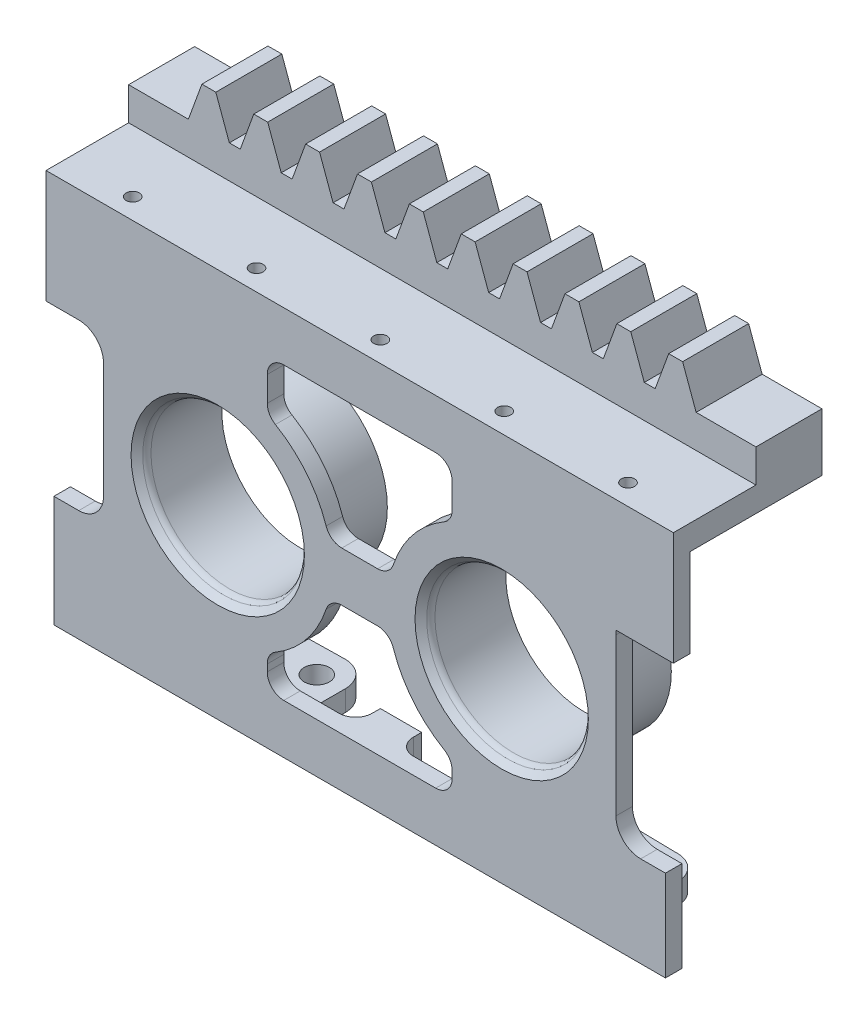
SolidWorks part; units mm, degrees
material "6061 合金"
ref_plane "Front" through (0, 0, 0) normal (0, 0, 1) x (1, 0, 0)
ref_plane "Top" through (0, 0, 0) normal (0, 1, 0) x (1, 0, 0)
ref_plane "Right" through (0, 0, 0) normal (1, 0, 0) x (0, 0, -1)
sketch "Sketch1" plane through (0, 0, 0) normal (0, 0, 1) x (1, 0, 0)
  line L1 (0, 0) -> (213.6283, 0)
  line L2 (0, 0) -> (0, -8)
  line L3 (0, -8) -> (213.6283, -8)
  line L4 (213.6283, 0) -> (213.6283, -8)
  dimension "D1" = 8
  dimension "L" = 213.6283
extrude "Extrude1" add sketch "Sketch1" along normal blind 8
sketch "Sketch2" plane through (0, 0, 8) normal (0, 0, 1) x (1, 0, 0)
  line L0 (0, 0) -> (1.6379, 4.5)
  line L1 (1.6379, 4.5) -> (3.3236, 4.5)
  line L2 (3.3236, 4.5) -> (4.9614, 0)
  line L3 (213.6283, 0) -> (0, 0) construction
  line L4 (0, 0) -> (4.9614, 0)
  line L5 (0.9099, 2.5) -> (4.0515, 2.5) construction
  dimension "alpha2" = 70
  dimension "alpha" = 110
  dimension "ha" = 2
  dimension "hf" = 2.5
  dimension "S" = 3.1416
extrude "Extrude2" add sketch "Sketch2" against normal up to surface (8 mm away) up to face at (106.8142, -4, 0)
pattern_linear "LPattern1" count 34 spacing 6.2832 along (1, 0, 0) of "Extrude2"
sketch "草图1" plane through (0, 0, 8) normal (0, 0, 1) x (1, 0, 0)
  line L1 (213.6283, -8) -> (74.0765, -8)
  line L2 (213.6283, -8) -> (213.6283, 20)
  line L3 (213.6283, 20) -> (74.0765, 20)
  line L4 (74.0765, -8) -> (74.0765, 20)
  dimension "D1" = 28
extrude "切除-拉伸1" cut sketch "草图1" against normal blind 10
sketch "草图2" plane through (0, 0, 0) normal (0, 1, 0) x (1, 0, 0)
  line L1 (0, 0) -> (4.9614, 0)
  line L2 (0, 0) -> (0, -8)
  line L3 (0, -8) -> (4.9614, -8)
  line L4 (4.9614, 0) -> (4.9614, -8)
  line L5 (69.115, 0) -> (74.0765, 0)
  line L6 (69.115, 0) -> (69.115, -8)
  line L7 (69.115, -8) -> (74.0765, -8)
  line L8 (74.0765, 0) -> (74.0765, -8)
extrude "切除-拉伸2" cut sketch "草图2" along normal blind 10
sketch "草图3" plane through (0, 0, 8) normal (0, 0, 1) x (1, 0, 0)
  line L0 (0, 0) -> (0, -8) construction
  line L1 (0, -7) -> (74.0765, -7)
  line L2 (0, -7) -> (0, -8)
  line L3 (0, -8) -> (74.0765, -8)
  line L4 (74.0765, -7) -> (74.0765, -8)
  line L5 (74.0765, 0) -> (67.7933, 0) construction
  dimension "D1" = 7
extrude "切除-拉伸3" cut sketch "草图3" against normal blind 10
sketch "草图4" plane through (0, 0, 8) normal (0, 0, 1) x (1, 0, 0)
  line L0 (74.0765, 0) -> (74.0765, -7) construction
  line L1 (0, -7) -> (74.0765, -7)
  line L2 (0, -7) -> (0, -5)
  line L3 (0, -5) -> (74.0765, -5)
  line L4 (74.0765, -7) -> (74.0765, -5)
  dimension "D1" = 2
extrude "凸台-拉伸1" add sketch "草图4" along normal blind 8
sketch "草图5" plane through (0, 0, 16) normal (0, 0, 1) x (1, 0, 0)
  line L0 (74.0765, -7) -> (74.0765, -5) construction
  line L1 (0, -5) -> (74.0765, -5)
  line L2 (0, -5) -> (0, -50.4)
  line L3 (0, -50.4) -> (74.0765, -50.4)
  line L4 (74.0765, -5) -> (74.0765, -50.4)
  dimension "D1" = 45.4
extrude "凸台-拉伸2" add sketch "草图5" along normal blind 2
sketch "草图6" plane through (0, -50.4, 0) normal (0, -1, 0) x (1, 0, 0)
  line L0 (26.8382, 9.55) -> (26.8382, 11.9) construction
  line L1 (26.8382, 9.55) -> (26.8382, 18)
  line L2 (6.8382, 14.8) -> (6.8382, 9.6986) construction
  line L3 (6.8382, 18) -> (6.8382, 9.6986)
  line L4 (9.7846, 6.6991) -> (23.6828, 6.4505)
  line L5 (0, 18) -> (74.0765, 18) construction
  line L6 (6.8382, 18) -> (26.8382, 18)
  arc A0 (22.714, 10.1818) -> (24.5625, 9.4182) centre (23.6382, 9.8) ccw construction
  arc A1 (10.0382, 8.8) -> (10.0382, 10.8) centre (10.0382, 9.8) ccw construction
  arc A2 (22.714, 10.1818) -> (24.5625, 9.4182) centre (23.6382, 9.8) ccw construction
  arc A3 (10.0382, 8.8) -> (10.0382, 10.8) centre (10.0382, 9.8) ccw construction
  arc A4 (25.5982, 7.07) -> (26.8382, 9.55) centre (23.7382, 9.55) ccw construction
  arc A5 (23.6828, 6.4505) -> (26.8382, 9.55) centre (23.7382, 9.55) ccw
  arc A6 (6.8382, 9.6986) -> (8.2948, 7.1261) centre (9.8382, 9.6986) ccw construction
  arc A7 (6.8382, 9.6986) -> (9.7846, 6.6991) centre (9.8382, 9.6986) ccw
  circle A8 centre (10.0382, 9.8) radius 1.525
  circle A9 centre (23.6382, 9.8) radius 1.525
  dimension "D1" = 3.05
extrude "凸台-拉伸3" add sketch "草图6" against normal blind 1.7
ref_plane "基准面1" through (37.0382, 0, 0) normal (-1, 0, 0) x (0, 0, 1)
mirror "镜向1" about plane through (37.0382, 0, 0) normal (-1, 0, 0) of "凸台-拉伸3"
sketch "草图7" plane through (0, 0, 18) normal (0, 0, 1) x (1, 0, 0)
  arc A0 (54.2382, -18.15) -> (43.7357, -27.7) centre (54.2382, -28.7) ccw construction
  arc A1 (30.3407, -27.7) -> (19.8382, -18.15) centre (19.8382, -28.7) ccw construction
  arc A2 (54.2382, -18.15) -> (43.7357, -27.7) centre (54.2382, -28.7) ccw construction
  arc A3 (30.3407, -27.7) -> (19.8382, -18.15) centre (19.8382, -28.7) ccw construction
  circle A4 centre (54.2382, -28.7) radius 10.55
  circle A5 centre (19.8382, -28.7) radius 10.55
  circle A6 centre (54.2382, -28.7) radius 9.5
  circle A7 centre (19.8382, -28.7) radius 9.5
  dimension "D1" = 21.1
  dimension "D2" = 19
extrude "凸台-拉伸4" add sketch "草图7" against normal blind 10
sketch "草图8" plane through (0, 0, 16) normal (0, 0, -1) x (-1, 0, 0)
  circle A1 centre (-19.8382, -28.7) radius 9.5
  circle A2 centre (-19.8382, -28.7) radius 9.5
  circle A3 centre (-54.2382, -28.7) radius 9.5
  circle A4 centre (-54.2382, -28.7) radius 9.5
  dimension "D1" = 0
  dimension "D2" = 0
extrude "切除-拉伸4" cut sketch "草图8" against normal blind 7
sketch "草图9" plane through (0, 0, 18) normal (0, 0, 1) x (1, 0, 0)
  line L0 (0, -5) -> (0, -50.4) construction
  line L1 (-6, -37.7) -> (6, -37.7)
  line L2 (-6, -37.7) -> (-6, -17.7)
  line L3 (-6, -17.7) -> (6, -17.7)
  line L4 (6, -37.7) -> (6, -17.7)
  line L5 (-6, -37.7) -> (6, -17.7) construction
  line L6 (-6, -17.7) -> (6, -37.7) construction
  line L7 (74.0765, -50.4) -> (74.0765, -5) construction
  line L8 (68.0765, -40.2) -> (80.0765, -40.2)
  line L9 (68.0765, -40.2) -> (68.0765, -15.2)
  line L10 (68.0765, -15.2) -> (80.0765, -15.2)
  line L11 (80.0765, -40.2) -> (80.0765, -15.2)
  line L12 (68.0765, -40.2) -> (80.0765, -15.2) construction
  line L13 (68.0765, -15.2) -> (80.0765, -40.2) construction
  point P0 (0, -27.7)
  point P7 (74.0765, -27.7)
  dimension "D1" = 25
  dimension "D2" = 20
  dimension "D3" = 12
extrude "切除-拉伸5" cut sketch "草图9" against normal blind 7
fillet "圆角1" radius 3 4 edges at (68.0765, -15.2, 17) (68.0765, -40.2, 17) (6, -17.7, 17) (6, -37.7, 17)
sketch "草图10" plane through (0, -50.4, 0) normal (0, -1, 0) x (1, 0, 0)
  line L0 (37.0382, 16) -> (37.0382, 6) construction
  line L1 (26.8382, 16) -> (47.2382, 16) construction
  line L2 (37.0382, 9.185) -> (37.0382, -9.185) construction
  line L4 (34.0382, 6) -> (40.0382, 6)
  line L5 (34.0382, 6) -> (34.0382, 16)
  line L6 (34.0382, 16) -> (40.0382, 16)
  line L7 (40.0382, 6) -> (40.0382, 16)
  line L8 (34.0382, 6) -> (40.0382, 16) construction
  line L9 (34.0382, 16) -> (40.0382, 6) construction
  point P6 (37.0382, 11)
  dimension "D1" = 6
  dimension "D2" = 10
extrude "凸台-拉伸5" [suppressed] add sketch "草图10" against normal blind 2 and the other way blind 0.8
sketch "草图12" [suppressed] plane through (0, -49.4, 0) normal (0, -1, 0) x (1, 0, 0)
  line L0 (0, 18) -> (74.0765, 18) construction
  line L1 (34.0382, 16) -> (40.0382, 16)
  line L2 (34.0382, 16) -> (34.0382, 18)
  line L3 (34.0382, 18) -> (40.0382, 18)
  line L4 (40.0382, 16) -> (40.0382, 18)
  line L5 (40.0382, 6) -> (40.0382, 16) construction
extrude "凸台-拉伸6" [suppressed] add sketch "草图12" along normal up to surface (0.8 mm away) up to face at (72.5057, 0, 4)
fillet "圆角2" [suppressed] radius 3
sketch "草图13" plane through (0, -50.4, 0) normal (0, -1, 0) x (1, 0, 0)
  line L12 (74.0765, 16) -> (74.0765, 18)
  line L13 (74.0765, 18) -> (0, 18)
  line L14 (0, 18) -> (0, 16)
  line L15 (0, 16) -> (6.8382, 16)
  line L16 (6.8382, 16) -> (6.8382, 9.6986)
  line L17 (9.7846, 6.6991) -> (23.6828, 6.4505)
  line L18 (26.8382, 9.55) -> (26.8382, 16)
  line L19 (26.8382, 16) -> (47.2382, 16)
  line L20 (47.2382, 16) -> (47.2382, 9.55)
  line L21 (50.3937, 6.4505) -> (64.2919, 6.6991)
  line L22 (67.2382, 9.6986) -> (67.2382, 16)
  line L23 (67.2382, 16) -> (74.0765, 16)
  line L24 (74.0765, 16) -> (74.0765, 18)
  line L25 (74.0765, 18) -> (0, 18)
  line L26 (0, 18) -> (0, 16)
  line L27 (0, 16) -> (6.8382, 16)
  line L28 (6.8382, 16) -> (6.8382, 9.6986)
  line L29 (9.7846, 6.6991) -> (23.6828, 6.4505)
  line L30 (26.8382, 9.55) -> (26.8382, 16)
  line L31 (26.8382, 16) -> (47.2382, 16)
  line L32 (47.2382, 16) -> (47.2382, 9.55)
  line L33 (50.3937, 6.4505) -> (64.2919, 6.6991)
  line L34 (67.2382, 9.6986) -> (67.2382, 16)
  line L35 (67.2382, 16) -> (74.0765, 16)
  circle A0 centre (64.0382, 9.8) radius 1.525 construction
  circle A1 centre (50.4382, 9.8) radius 1.525 construction
  circle A2 centre (23.6382, 9.8) radius 1.525 construction
  circle A3 centre (10.0382, 9.8) radius 1.525 construction
  arc A4 (6.8382, 9.6986) -> (9.7846, 6.6991) centre (9.8382, 9.6986) ccw
  arc A5 (23.6828, 6.4505) -> (26.8382, 9.55) centre (23.7382, 9.55) ccw
  arc A6 (47.2382, 9.55) -> (50.3937, 6.4505) centre (50.3382, 9.55) ccw
  arc A7 (64.2919, 6.6991) -> (67.2382, 9.6986) centre (64.2382, 9.6986) ccw
  arc A8 (6.8382, 9.6986) -> (9.7846, 6.6991) centre (9.8382, 9.6986) ccw
  arc A9 (23.6828, 6.4505) -> (26.8382, 9.55) centre (23.7382, 9.55) ccw
  arc A10 (47.2382, 9.55) -> (50.3937, 6.4505) centre (50.3382, 9.55) ccw
  arc A11 (64.2919, 6.6991) -> (67.2382, 9.6986) centre (64.2382, 9.6986) ccw
  circle A12 centre (64.0382, 9.8) radius 1.525
  circle A13 centre (50.4382, 9.8) radius 1.525
  circle A14 centre (23.6382, 9.8) radius 1.525
  circle A15 centre (10.0382, 9.8) radius 1.525
  dimension "D1" = 0
extrude "凸台-拉伸7" add sketch "草图13" along normal blind 0.8
sketch "草图14" plane through (0, 0, 0) normal (-1, 0, 0) x (0, 0, 1)
  line L8 (16, -7) -> (16, -17.7)
  line L9 (16, -17.7) -> (18, -17.7)
  line L10 (18, -17.7) -> (18, -5)
  line L11 (18, -5) -> (8, -5)
  line L12 (8, -5) -> (8, 0)
  line L13 (8, 0) -> (0, 0)
  line L14 (0, 0) -> (0, -7)
  line L15 (0, -7) -> (16, -7)
  line L16 (16, -7) -> (16, -17.7)
  line L17 (16, -17.7) -> (18, -17.7)
  line L18 (18, -17.7) -> (18, -5)
  line L19 (18, -5) -> (8, -5)
  line L20 (8, -5) -> (8, 0)
  line L21 (8, 0) -> (0, 0)
  line L22 (0, 0) -> (0, -7)
  line L23 (0, -7) -> (16, -7)
  dimension "D1" = 0
extrude "凸台-拉伸8" add sketch "草图14" against normal offset from surface (75.0382 mm away) 38 up to plane "基准面1" offset beyond the face yes
sketch "草图15" plane through (74.0765, 0, 0) normal (1, 0, 0) x (0, 0, -1)
  line L13 (-16, -7) -> (0, -7)
  line L14 (0, -7) -> (0, 0)
  line L15 (0, 0) -> (-8, 0)
  line L24 (-8, 0) -> (-8, -5)
  line L25 (-8, -5) -> (-18, -5)
  line L26 (-18, -5) -> (-18, -17.7)
  line L27 (-18, -17.7) -> (-16, -17.7)
  line L28 (-16, -17.7) -> (-16, -7)
  line L29 (-16, -7) -> (0, -7)
  line L30 (0, -7) -> (0, 0)
  line L31 (0, 0) -> (-8, 0)
  line L32 (-8, 0) -> (-8, -5)
  line L33 (-8, -5) -> (-18, -5)
  line L34 (-18, -5) -> (-18, -17.7)
  line L35 (-18, -17.7) -> (-16, -17.7)
  line L36 (-16, -17.7) -> (-16, -7)
  dimension "D1" = 0
extrude "凸台-拉伸9" add sketch "草图15" against normal offset from surface (75.0382 mm away) 38 up to plane "基准面1"
sketch "草图16" plane through (0, -5, 0) normal (0, 1, 0) x (1, 0, 0)
  line L4 (-0.9618, -8) -> (-0.9618, -18)
  line L5 (-0.9618, -18) -> (75.0382, -18)
  line L6 (75.0382, -18) -> (75.0382, -8)
  line L7 (75.0382, -8) -> (-0.9618, -8)
  line L8 (-0.9618, -8) -> (-0.9618, -18)
  line L9 (-0.9618, -18) -> (75.0382, -18)
  line L10 (75.0382, -18) -> (75.0382, -8)
  line L11 (75.0382, -8) -> (-0.9618, -8)
  dimension "D1" = 0
extrude "凸台-拉伸10" add sketch "草图16" along normal blind 1
sketch "草图17" plane through (0, -51.2, 0) normal (0, -1, 0) x (1, 0, 0)
  line L0 (74.0765, 18) -> (0, 18) construction
  line L1 (34.5382, 18) -> (39.5382, 18)
  line L2 (34.5382, 18) -> (34.5382, 13)
  line L3 (34.5382, 13) -> (39.5382, 13)
  line L4 (39.5382, 18) -> (39.5382, 13)
  line L5 (37.0382, 16) -> (37.0382, 13) construction
  line L6 (-0.9618, 16) -> (75.0382, 16) construction
  line L7 (26.8382, 16) -> (47.2382, 16) construction
  dimension "D1" = 5
  dimension "D2" = 3
extrude "凸台-拉伸11" add sketch "草图17" against normal blind 6
sketch "草图18" plane through (0, -51.2, 0) normal (0, -1, 0) x (1, 0, 0)
  line L0 (37.0382, 15.5) -> (37.0382, 2.607) construction
  circle A0 centre (22.0382, 15.5) radius 1.2 construction
  circle A1 centre (22.0382, 15.5) radius 1.2
  circle A2 centre (37.0382, 15.5) radius 1.8 construction
  circle A3 centre (37.0382, 15.5) radius 1.8
  circle A4 centre (52.0382, 15.5) radius 1.2
hole_wizard "M2 螺纹孔1" positions "草图19" profile "草图20" tap size "M2" standard "GB"
sketch "草图19" plane through (0, -51.2, 0) normal (0, -1, 0) x (-1, 0, 0)
  point P0 (-22.0382, -15.5)
  point P3 (-52.0382, -15.5)
  point P7 (-37.0382, -15.5)
sketch "草图20" plane through (22.0382, -51.2, 15.5) normal (1, 0, 0) x (0, 0, -1)
  line L0 (0, 0) -> (0, 5.6807)
  line L1 (0, 5.6807) -> (0.8, 5.2)
  line L2 (0.8, 5.2) -> (0.8, 0)
  line L5 (0.8, 0) -> (0, 0)
  line L10 (0, 5.6807) -> (-0.8, 5.2) construction
  line L11 (0, -6.35) -> (0, 107.95) construction
  dimension "螺纹孔钻头直径" = 1.6
  dimension "螺纹孔钻头深度" = 5.2
  dimension "导头角度" = 118
cosmetic thread "孔螺蚊线1" parameters "D1"=4, "D2"=2
cosmetic thread "孔螺蚊线2" parameters "D1"=4, "D2"=2
cosmetic thread "孔螺蚊线3" parameters "D1"=4, "D2"=2
fillet "圆角3" radius 2 2 edges at (34.5382, -48.2, 16) (39.5382, -48.2, 16)
sketch "草图22" plane through (0, -4, 0) normal (0, 1, 0) x (1, 0, 0)
  line L0 (37.0382, -15.5) -> (37.0382, -20.0975) construction
  circle A0 centre (37.0382, -15.5) radius 1.2 construction
  circle A1 centre (22.0382, -15.5) radius 1.2 construction
  circle A2 centre (7.0382, -15.5) radius 1.2 construction
  circle A3 centre (37.0382, -15.5) radius 1.2
  circle A4 centre (22.0382, -15.5) radius 1.2
  circle A5 centre (7.0382, -15.5) radius 1.2
  circle A6 centre (67.0382, -15.5) radius 1.2
  circle A7 centre (52.0382, -15.5) radius 1.2
hole_wizard "M2 螺纹孔2" positions "草图23" profile "草图24" tap size "M2" standard "GB"
sketch "草图23" plane through (0, -4, 0) normal (0, 1, 0) x (1, 0, 0)
  point P0 (7.0382, -15.5)
  point P3 (22.0382, -15.5)
  point P6 (37.0382, -15.5)
  point P9 (52.0382, -15.5)
  point P12 (67.0382, -15.5)
sketch "草图24" plane through (7.0382, -4, 15.5) normal (1, 0, 0) x (0, 0, 1)
  line L0 (0, 0) -> (0, 5.6807)
  line L1 (0, 5.6807) -> (0.8, 5.2)
  line L2 (0.8, 5.2) -> (0.8, 0)
  line L5 (0.8, 0) -> (0, 0)
  line L10 (0, 5.6807) -> (-0.8, 5.2) construction
  line L11 (0, -6.35) -> (0, 107.95) construction
  dimension "螺纹孔钻头直径" = 1.6
  dimension "螺纹孔钻头深度" = 5.2
  dimension "导头角度" = 118
cosmetic thread "孔螺蚊线4" parameters "D1"=4, "D2"=2
cosmetic thread "孔螺蚊线5" parameters "D1"=4, "D2"=2
cosmetic thread "孔螺蚊线6" parameters "D1"=4, "D2"=2
cosmetic thread "孔螺蚊线7" parameters "D1"=4, "D2"=2
cosmetic thread "孔螺蚊线8" parameters "D1"=4, "D2"=2
chamfer "倒角1" distance 1 angle 45 2 edges at (29.3382, -28.7, 18) (63.7382, -28.7, 18)
fillet "圆角5" radius 1 2 edges at (63.7382, -28.7, 17) (29.3382, -28.7, 17)
sketch "草图25" plane through (0, 0, 16) normal (0, 0, -1) x (-1, 0, 0)
  line L0 (-6, -34.7) -> (-6, -20.7) construction
  line L1 (-48.2382, -16.2302) -> (-48.2382, -10)
  line L2 (-48.2382, -10) -> (-25.8382, -10)
  line L3 (-25.8382, -10) -> (-25.8382, -16.2302)
  line L4 (-22.6627, -7) -> (-36.4137, -7) construction
  line L5 (-37.0382, -10) -> (-37.0382, -45.2) construction
  line L6 (-34.5382, -45.2) -> (-39.5382, -45.2) construction
  line L7 (-48.2382, -41.1698) -> (-48.2382, -45.2)
  line L8 (-48.2382, -45.2) -> (-25.8382, -45.2)
  line L9 (-25.8382, -45.2) -> (-25.8382, -41.1698)
  arc A0 (-48.2382, -41.1698) -> (-48.2382, -16.2302) centre (-54.2382, -28.7) ccw
  arc A1 (-25.8382, -16.2302) -> (-25.8382, -41.1698) centre (-19.8382, -28.7) ccw
  dimension "D1" = 3
  dimension "D2" = 6
extrude "切除-拉伸6" cut sketch "草图25" against normal blind 10
sketch "草图26" plane through (0, 0, 16) normal (0, 0, -1) x (-1, 0, 0)
  line L0 (-40.4, -28.7) -> (-33.6765, -28.7) construction
  line L1 (-40.7291, -31.7) -> (-33.3474, -31.7)
  line L2 (-40.7291, -25.7) -> (-33.3474, -25.7)
  line L3 (-40.4, -25.7) -> (-33.6765, -25.7) construction
  line L4 (-40.4, -31.7) -> (-33.6765, -31.7) construction
  arc A0 (-48.2382, -41.1698) -> (-48.2382, -16.2302) centre (-54.2382, -28.7) ccw construction
  arc A1 (-25.8382, -16.2302) -> (-25.8382, -41.1698) centre (-19.8382, -28.7) ccw construction
  arc A2 (-33.3474, -25.7) -> (-33.3474, -31.7) centre (-19.8382, -28.7) ccw
  arc A3 (-40.7291, -31.7) -> (-40.7291, -25.7) centre (-54.2382, -28.7) ccw
  dimension "D1" = 3
  dimension "D2" = 3
extrude "凸台-拉伸12" add sketch "草图26" against normal up to surface (2 mm away) up to face at (37.0382, -28.15, 18)
fillet "圆角6" radius 2 12 edges at (48.2382, -16.2302, 17) (48.2382, -10, 17) (25.8382, -10, 17) (25.8382, -16.2302, 17) (40.7291, -25.7, 17) (33.3474, -25.7, 17) (33.3474, -31.7, 17) (25.8382, -41.1698, 17) (48.2382, -41.1698, 17) (40.7291, -31.7, 17) (48.2382, -45.2, 17) (25.8382, -45.2, 17)
